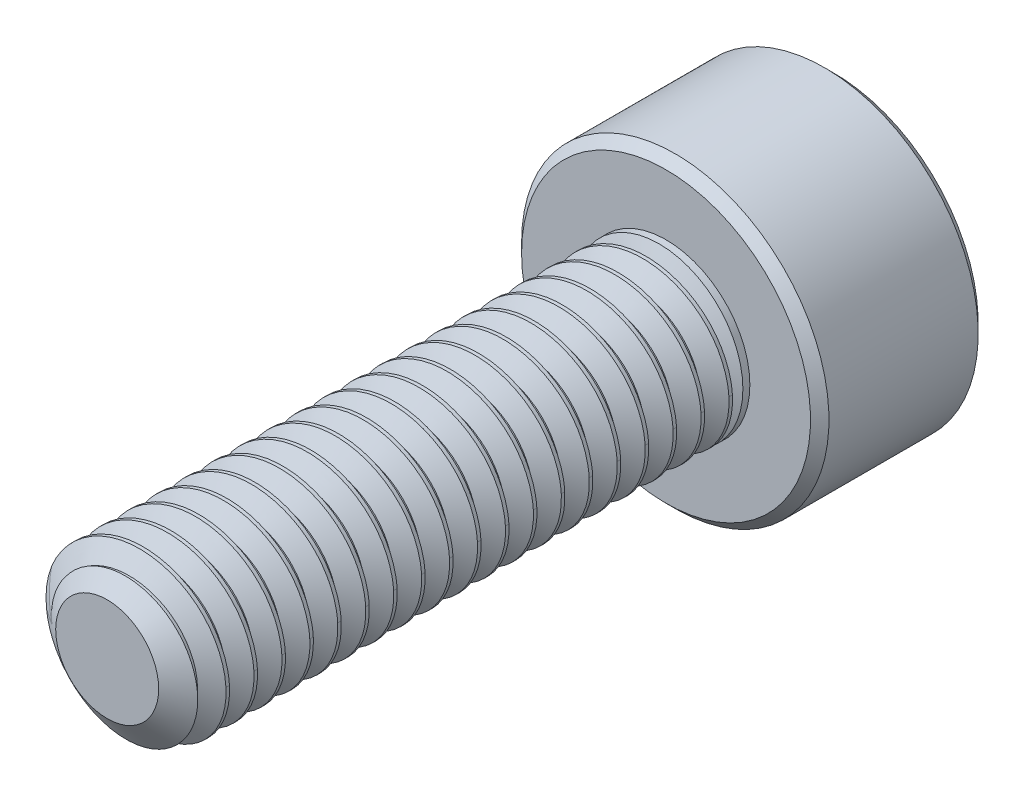
SolidWorks part; units mm, degrees
material "1023 Carbon Steel Sheet (SS)"
ref_plane "Front Plane" through (0, 0, 0) normal (0, 0, 1) x (1, 0, 0)
ref_plane "Top Plane" through (0, 0, 0) normal (0, 1, 0) x (1, 0, 0)
ref_plane "Right Plane" through (0, 0, 0) normal (1, 0, 0) x (0, 0, -1)
sketch "Sketch1" plane through (0, 0, 0) normal (0, 0, 1) x (1, 0, 0)
  circle A0 centre (0, 0) radius 1.5
  dimension "OD" = 3
extrude "Extrude1" add sketch "Sketch1" against normal blind 10
sketch "Sketch2" plane through (0, 0, 0) normal (0, 0, 1) x (1, 0, 0)
  circle A0 centre (0, 0) radius 1.5 construction
  circle A1 centre (0, 0) radius 1.5
curve "Helix/Spiral1" pitch 0.5 height 10.5 radius 1.5 centre (0, 0, 0) axis (0, 0, -1) start towards (0, 1, 0) parameters "pitch"=0.5
sketch "Sketch3" plane through (0, 0, 0) normal (1, 0, 0) x (0, 0, -1)
  line L0 (-0.4375, 1.5) -> (-0.25, 1.1752)
  line L1 (-0.25, 1.1752) -> (-0.1875, 1.1752)
  line L2 (-0.1875, 1.1752) -> (0, 1.5)
  line L3 (-0.4375, 1.5) -> (0, 1.5)
  line L4 (-0.2187, 1.5) -> (-0.2187, 1.1752) construction
  line L5 (-0.3437, 1.3376) -> (-0.0937, 1.3376) construction
  line L6 (0, 1.5) -> (0, -1.5) construction
  line L7 (0, -1.5) -> (10, -1.5) construction
  point P11 (2.25, -1.5)
  dimension "D1" = 0.0625
  dimension "D2" = 0.25
  dimension "D3" = 60
  dimension "D4" = 2.25
sweep "Cut-Sweep1" cut profiles "Sketch3" path "Helix/Spiral1" align with end faces yes
sketch "Sketch4" plane through (0, 0, 0) normal (1, 0, 0) x (0, 0, -1)
  line L0 (0.4053, 1.5) -> (0, 0.9212)
  line L1 (0, 0.9212) -> (0, 1.5)
  line L2 (0.4053, 1.5) -> (0, 1.5)
  line L3 (-0.4375, 1.5) -> (0, 1.5) construction
  line L4 (0, 0) -> (7.0209, 0) construction
  dimension "D1" = 55
  dimension "D2" = 0.254
revolve "Cut-Revolve1" cut sketch "Sketch4" angle 360 about L4
sketch "Sketch5" plane through (0, 0, 0) normal (1, 0, 0) x (0, 0, -1)
  line L0 (10, -1.1822) -> (10, 1.0703) construction
  line L1 (10, 1.5) -> (0.1203, 1.5)
  line L2 (10, 1.5) -> (10, 0)
  line L3 (10, 0) -> (0.0001, 0)
  line L4 (0.0001, 1.1698) -> (0.0001, 0)
  line L5 (0.1203, 1.5) -> (0.0001, 1.1698)
  line L6 (0, 0) -> (9.9695, 0) construction
  point P3 (0.0001, 1.5)
  point P10 (0.0001, 1.5)
  dimension "D1" = 0.3302
  dimension "Thread min" = 0.0001
  dimension "D3" = 20
revolve "partially thread" [suppressed] add sketch "Sketch5" angle 360 about L6
sketch "Sketch6" plane through (0, 0, -10) normal (0, 0, -1) x (-1, 0, 0)
  circle A0 centre (0, 0) radius 2.75
  dimension "head dia" = 5.5
extrude "Extrude2" add sketch "Sketch6" along normal blind 3
sketch "Sketch7" plane through (0, 0, -13) normal (0, 0, -1) x (-1, 0, 0)
  line L1 (0, 1.4434) -> (-1.25, 0.7217)
  line L2 (-1.25, 0.7217) -> (-1.25, -0.7217)
  line L3 (-1.25, -0.7217) -> (0, -1.4434)
  line L4 (0, -1.4434) -> (1.25, -0.7217)
  line L5 (1.25, -0.7217) -> (1.25, 0.7217)
  line L6 (1.25, 0.7217) -> (0, 1.4434)
  circle A0 centre (0, 0) radius 1.25 construction
  dimension "hex dia" = 2.5
extrude "Cut-Extrude1" cut sketch "Sketch7" against normal blind 1.875
sketch "Sketch8" plane through (0, 0, -13) normal (0, 0, -1) x (-1, 0, 0)
  circle A0 centre (0, 0) radius 1.4434
extrude "Cut-Extrude2" cut sketch "Sketch8" against normal through all draft 45
chamfer "Chamfer1" distance 0.165 angle 45 2 edges at (-2.75, 0, -13) (-2.75, 0, -10)
sketch "Sketch9" plane through (0, 0, 0) normal (1, 0, 0) x (0, 0, -1)
  line L0 (0, 1.5) -> (0, -1.5) construction
  line L1 (2.75, 1.5) -> (2.75, -1.5) construction
  dimension "D1" = 2.75
sketch "Sketch10" plane through (0, 0, 0) normal (1, 0, 0) x (0, 0, -1)
  line L0 (10, 1.5) -> (10, 0)
  line L1 (10, 1.5) -> (9.875, 1.5)
  line L2 (9.875, 1.5) -> (9.2537, 0)
  line L3 (10, 0) -> (9.2537, 0)
  line L4 (10, 2.585) -> (10, -2.585) construction
  dimension "D1" = 22.5
  dimension "D2" = 0.125
revolve "Revolve1" add sketch "Sketch10" angle 360 about L3
move or copy body "Body-Move/Copy1" [suppressed] bodies to move or copy 108
equation "\"D3@Helix/Spiral1\" = \"screw length@Extrude1\"+\"pitch@Helix/Spiral1\""
equation "\"D1@Sketch3\" = \"pitch@Helix/Spiral1\"*.125"
equation "\"D2@Sketch3\" = \"pitch@Helix/Spiral1\"*.5"
equation "\"D1@Cut-Extrude1\" = \"hex dia@Sketch7\"*.75"
equation "\"D1@Chamfer1\" = \"head dia@Sketch6\"*.03"
equation "\"D1@Sketch9\" = \"pitch@Helix/Spiral1\"*5.5"
equation "\"D2@Sketch10\" = \"pitch@Helix/Spiral1\"*.25"
equation "\"D4@Sketch3\" = \"pitch@Helix/Spiral1\"*4.50"
